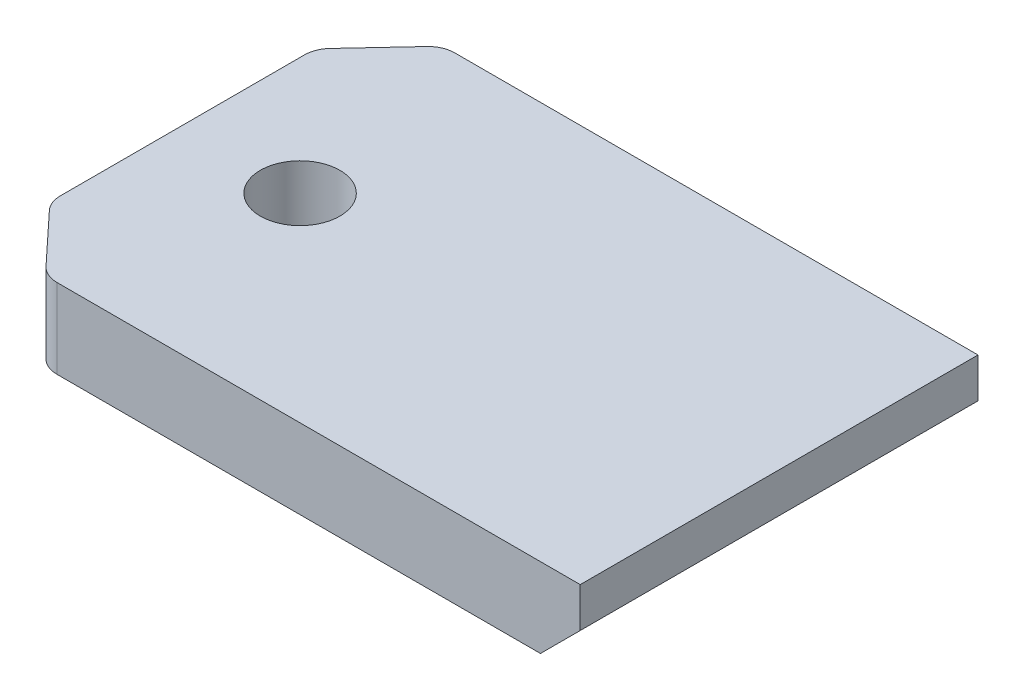
SolidWorks part; units mm, degrees
ref_plane "Спереди" through (0, 0, 0) normal (0, 0, 1) x (1, 0, 0)
ref_plane "Сверху" through (0, 0, 0) normal (0, 1, 0) x (1, 0, 0)
ref_plane "Справа" through (0, 0, 0) normal (1, 0, 0) x (0, 0, -1)
sketch "Эскиз1" plane through (0, 0, 0) normal (1, 0, 0) x (0, 0, -1)
  line L1 (0, 0) -> (30, 0)
  line L2 (0, 0) -> (0, -6)
  line L3 (0, -6) -> (30, -6)
  line L4 (30, 0) -> (30, -6)
extrude "Вытянуть1" add sketch "Эскиз1" along normal blind 45
chamfer "Фаска1" distance 3 angle 45 1 edges at (45, -6, -15)
sketch "Эскиз2" plane through (0, 0, 0) normal (0, 1, 0) x (-1, 0, 0)
  line L0 (-10.5597, -15) -> (-7.257, -15) construction
  circle A0 centre (-8.8699, -15) radius 3
extrude "Вырез-Вытянуть1" cut sketch "Эскиз2" against normal through all
chamfer "Фаска2" distance 5 angle 43 2 edges at (0, -3, -30) (0, -3, 0) first distance on face at (0, -3, -15)
fillet "Скругление1" radius 2 4 edges at (4.6626, -3, 0) (0, -3, -5) (0, -3, -25) (4.6626, -3, -30)
